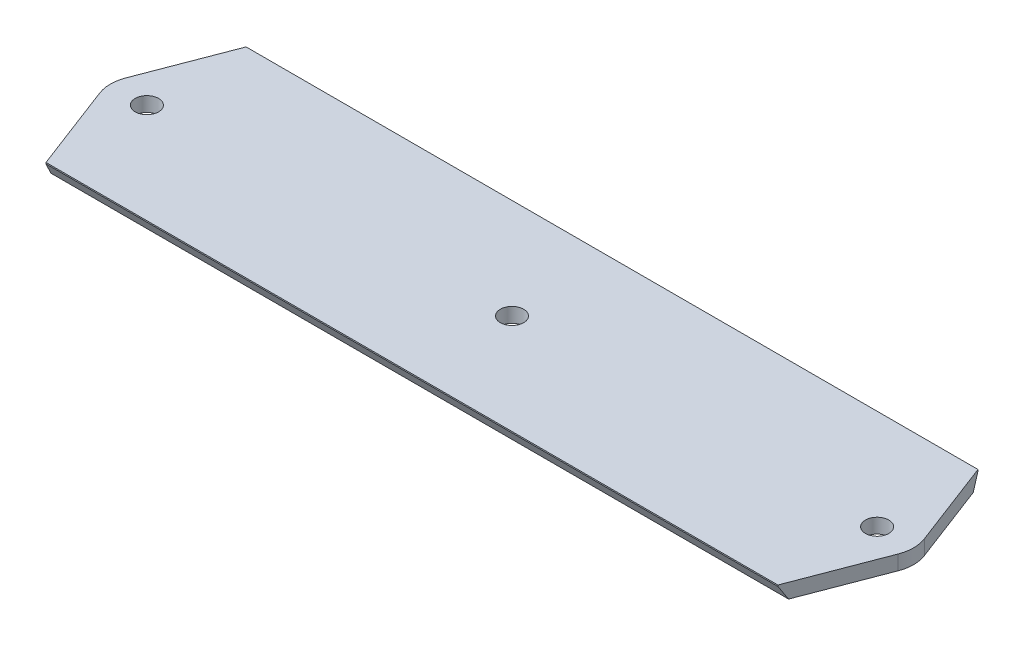
SolidWorks part; units mm, degrees
material "Медь"
ref_plane "Front" through (0, 0, 0) normal (0, 0, 1) x (1, 0, 0)
ref_plane "Top" through (0, 0, 0) normal (0, 1, 0) x (1, 0, 0)
ref_plane "Right" through (0, 0, 0) normal (1, 0, 0) x (0, 0, -1)
sketch "Эскиз1" plane through (0, 0, 0) normal (0, 1, 0) x (1, 0, 0)
  line L0 (-75, 14) -> (-79.6702, 1.7857)
  line L1 (-75, -14) -> (25, -14)
  line L2 (-75, 14) -> (25, -14) construction
  line L3 (25, 14) -> (-75, -14) construction
  line L4 (-75, -14) -> (-75, -1.6)
  line L7 (-75, -14) -> (-79.6702, -1.7857)
  line L8 (-75, 1.6) -> (-75, 14)
  line L9 (0, 0) -> (0, 14) construction
  line L16 (-75, 14) -> (25, 14)
  line L18 (25, 14) -> (29.6702, 1.7857)
  line L19 (25, -14) -> (29.6702, -1.7857)
  circle A0 centre (-75, 0) radius 1.6
  arc A1 (-79.6702, 1.7857) -> (-79.6702, -1.7857) centre (-75, 0) ccw
  arc A2 (29.6702, -1.7857) -> (29.6702, 1.7857) centre (25, 0) ccw
  circle A4 centre (-25, 0) radius 1.6
  circle A5 centre (25, 0) radius 1.6
  point P0 (0, 0)
  dimension "D3" = 3.2
  dimension "D4" = 10
  dimension "D1" = 100
  dimension "D2" = 28
  dimension "D7" = 50
  dimension "D5" = 3
extrude "Бобышка-Вытянуть1" add sketch "Эскиз1" along normal blind 2
ref_plane "Плоскость1" through (-80, 0, 0) normal (-1, 0, 0) x (0, 0, 1)
sketch "Эскиз3" plane through (-80, 0, 0) normal (-1, 0, 0) x (0, 0, 1)
  line L0 (-12.6453, 0) -> (-14, 0)
  line L2 (-14, 0) -> (-14, 2)
  line L4 (14, 0) -> (14, 2)
  line L7 (-14, 2) -> (-13.8, 2)
  line L8 (-13.8, 2) -> (-12.6453, 0)
  line L9 (-14, 0) -> (-1.7857, 0)
  line L10 (14, 2) -> (13.8, 2)
  line L11 (13.8, 2) -> (12.6453, 0)
  line L12 (12.6453, 0) -> (14, 0)
  line L13 (14, 0) -> (14, 2) construction
  line L14 (-1.7857, 0) -> (-1.7857, 2)
  line L15 (-1.7857, 2) -> (-14, 2)
  line L16 (-14, 2) -> (-14, 0)
  line L17 (-14, 0) -> (-1.7857, 0)
  line L18 (-1.7857, 0) -> (-1.7857, 2)
  line L19 (-1.7857, 2) -> (-14, 2)
  line L20 (-14, 2) -> (-14, 0)
  line L21 (1.7857, 0) -> (14, 0)
  line L22 (14, 0) -> (14, 2)
  line L23 (14, 2) -> (1.7857, 2)
  line L24 (1.7857, 2) -> (1.7857, 0)
  line L25 (1.7857, 0) -> (14, 0)
  line L26 (14, 0) -> (14, 2)
  line L27 (14, 2) -> (1.7857, 2)
  line L28 (1.7857, 2) -> (1.7857, 0)
  dimension "D1" = 0.2
  dimension "D2" = 120
  dimension "D3" = 0
  dimension "D4" = 0
extrude "Вырез-Вытянуть1" cut sketch "Эскиз3" against normal through all contours L8 L7 L2 L0 | L11 L12 L4 L10
chamfer "Фаска1" distance 0.2 angle 30 1 edges at (-25, 2, -13.8)
chamfer "Фаска2" distance 0.2 angle 30 1 edges at (-25, 2, 13.8)
